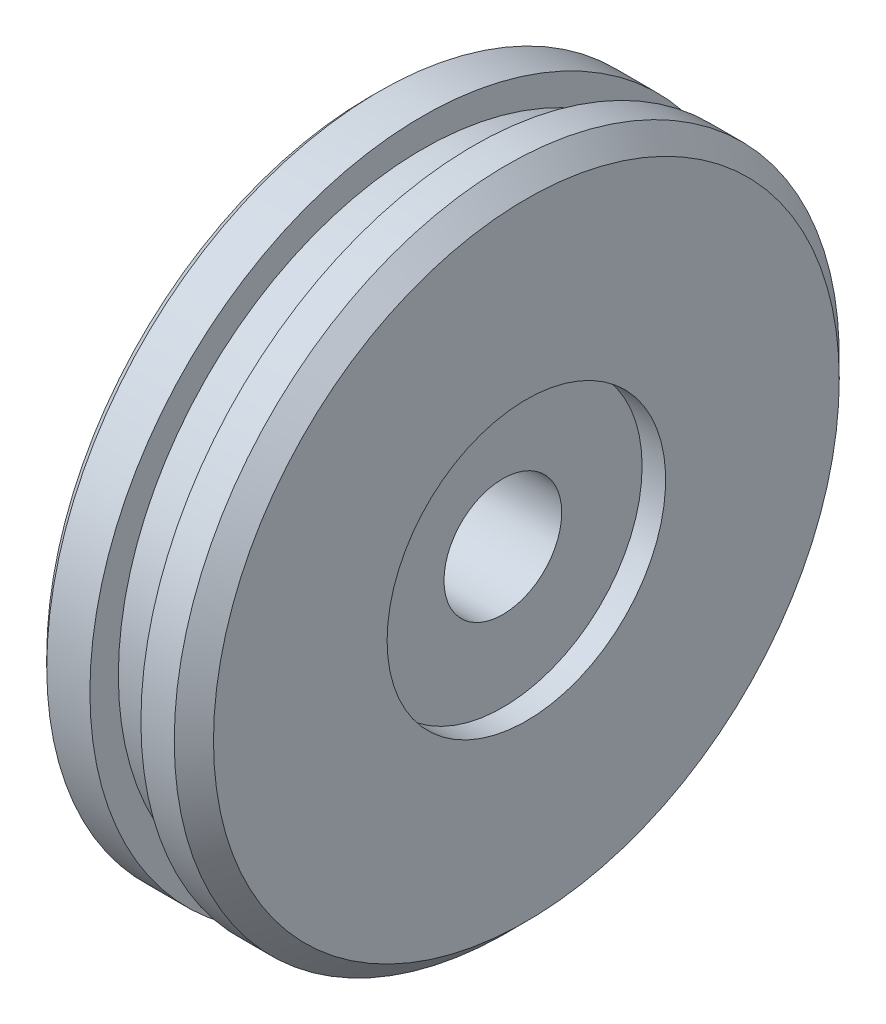
SolidWorks part; units mm, degrees
ref_plane "Front Plane" through (0, 0, 0) normal (0, 0, 1) x (1, 0, 0)
ref_plane "Top Plane" through (0, 0, 0) normal (0, 1, 0) x (1, 0, 0)
ref_plane "Right Plane" through (0, 0, 0) normal (1, 0, 0) x (0, 0, -1)
ref_plane "Plane1" through (0, 0, 66) normal (0, 0, 1) x (1, 0, 0)
sketch "Sketch1" plane through (0, 0, 66) normal (0, 0, 1) x (1, 0, 0)
  line L0 (72.2, -65) -> (90.2, -65) construction
  line L1 (77.2, -65) -> (85.2, -65)
  line L2 (85.2, -65) -> (85.2, -49.05)
  line L3 (85.2, -49.05) -> (84.2, -48.05)
  line L4 (84.2, -48.05) -> (77.7, -48.05)
  line L5 (77.7, -48.05) -> (77.2, -48.55)
  line L6 (77.2, -48.55) -> (77.2, -65)
revolve "Revolve1" add sketch "Sketch1" angle 360 about L0
sketch "Sketch2" plane through (0, 0, 66) normal (0, 0, 1) x (1, 0, 0)
  line L0 (74.9, -65) -> (87.5, -65) construction
  line L1 (79.9, -49.5) -> (82.5, -49.5)
  line L2 (82.5, -49.5) -> (82.5, -47.05)
  line L3 (82.5, -47.05) -> (79.9, -47.05)
  line L4 (79.9, -47.05) -> (79.9, -49.5)
revolve "Revolve2" add sketch "Sketch2" angle 360 about L0
combine bodies "Combine1" operation type subtract main body 101 bodies to subtract 102
sketch "Sketch3" plane through (0, 0, 0) normal (0, 0, 1) x (1, 0, 0)
  line L1 (76.7, -76.5) -> (79, -76.5)
  line L2 (76.7, -76.5) -> (76.7, -53.5)
  line L3 (76.7, -53.5) -> (79, -53.5)
  line L4 (79, -76.5) -> (79, -53.5)
extrude "Boss-Extrude1" add sketch "Sketch3" along normal blind 6.6 from offset 62.7 separate body
combine bodies "Combine2" operation type subtract main body 103 bodies to subtract 104
sketch "Sketch4" plane through (0, 0, 0) normal (0, 0, 1) x (1, 0, 0)
  line L1 (76.7, -68.3) -> (79, -68.3)
  line L2 (76.7, -68.3) -> (76.7, -61.7)
  line L3 (76.7, -61.7) -> (79, -61.7)
  line L4 (79, -68.3) -> (79, -61.7)
extrude "Boss-Extrude2" add sketch "Sketch4" along normal blind 23 from offset 54.5 separate body
combine bodies "Combine3" operation type subtract main body 105 bodies to subtract 106
sketch "Sketch5" plane through (0, 0, 0) normal (1, 0, 0) x (0, 0, -1)
  circle A0 centre (-66, -65) radius 4.6
extrude "Boss-Extrude3" add sketch "Sketch5" along normal blind 2.3 from offset 76.7 separate body
combine bodies "Combine4" operation type subtract main body 107 bodies to subtract 108
sketch "Sketch6" plane through (0, 0, 0) normal (1, 0, 0) x (0, 0, -1)
  circle A0 centre (-66, -65) radius 7.1
extrude "Boss-Extrude4" add sketch "Sketch6" along normal blind 1.7 from offset 84 separate body
combine bodies "Combine5" operation type subtract main body 109 bodies to subtract 110
sketch "Sketch7" plane through (0, 0, 0) normal (1, 0, 0) x (0, 0, -1)
  circle A0 centre (-66, -65) radius 3
extrude "Boss-Extrude5" add sketch "Sketch7" along normal blind 5.2 from offset 78.9 separate body
combine bodies "Combine6" operation type subtract main body 111 bodies to subtract 112
sketch "Sketch8" plane through (0, 0, 0) normal (0, 0, 1) x (1, 0, 0)
  line L1 (78.9, -59.5) -> (83, -59.5)
  line L2 (78.9, -59.5) -> (78.9, -57.4)
  line L3 (78.9, -57.4) -> (83, -57.4)
  line L4 (83, -59.5) -> (83, -57.4)
extrude "Boss-Extrude6" add sketch "Sketch8" along normal blind 1.8 from offset 65.1 separate body
combine bodies "Combine7" operation type subtract main body 113 bodies to subtract 114
sketch "Sketch9" plane through (0, 0, 0) normal (0, 0, 1) x (1, 0, 0)
  line L1 (78.9, -65.9) -> (83, -65.9)
  line L2 (78.9, -65.9) -> (78.9, -64.1)
  line L3 (78.9, -64.1) -> (83, -64.1)
  line L4 (83, -65.9) -> (83, -64.1)
extrude "Boss-Extrude7" add sketch "Sketch9" along normal blind 2.1 from offset 71.5 separate body
combine bodies "Combine8" operation type subtract main body 115 bodies to subtract 116
sketch "Sketch10" plane through (0, 0, 0) normal (0, 0, 1) x (1, 0, 0)
  line L1 (78.9, -72.6) -> (83, -72.6)
  line L2 (78.9, -72.6) -> (78.9, -70.5)
  line L3 (78.9, -70.5) -> (83, -70.5)
  line L4 (83, -72.6) -> (83, -70.5)
extrude "Boss-Extrude8" add sketch "Sketch10" along normal blind 1.8 from offset 65.1 separate body
combine bodies "Combine9" operation type subtract main body 117 bodies to subtract 118
sketch "Sketch11" plane through (0, 0, 0) normal (0, 0, 1) x (1, 0, 0)
  line L1 (78.9, -65.9) -> (83, -65.9)
  line L2 (78.9, -65.9) -> (78.9, -64.1)
  line L3 (78.9, -64.1) -> (83, -64.1)
  line L4 (83, -65.9) -> (83, -64.1)
extrude "Boss-Extrude9" add sketch "Sketch11" along normal blind 2.1 from offset 58.4 separate body
combine bodies "Combine10" operation type subtract main body 119 bodies to subtract 120
sketch "Sketch12" plane through (0, 0, 0) normal (0, 0, 1) x (1, 0, 0)
  line L1 (78.9, -57.4) -> (84.2, -57.4)
  line L2 (78.9, -57.4) -> (78.9, -55)
  line L3 (78.9, -55) -> (84.2, -55)
  line L4 (84.2, -57.4) -> (84.2, -55)
extrude "Boss-Extrude10" add sketch "Sketch12" along normal blind 1.8 from offset 65.1 separate body
combine bodies "Combine11" operation type subtract main body 121 bodies to subtract 122
sketch "Sketch13" plane through (0, 0, 0) normal (0, 0, 1) x (1, 0, 0)
  line L1 (78.9, -65.9) -> (84.2, -65.9)
  line L2 (78.9, -65.9) -> (78.9, -64.1)
  line L3 (78.9, -64.1) -> (84.2, -64.1)
  line L4 (84.2, -65.9) -> (84.2, -64.1)
extrude "Boss-Extrude11" add sketch "Sketch13" along normal blind 2.4 from offset 73.6 separate body
combine bodies "Combine12" operation type subtract main body 123 bodies to subtract 124
sketch "Sketch14" plane through (0, 0, 0) normal (0, 0, 1) x (1, 0, 0)
  line L1 (78.9, -75) -> (84.2, -75)
  line L2 (78.9, -75) -> (78.9, -72.6)
  line L3 (78.9, -72.6) -> (84.2, -72.6)
  line L4 (84.2, -75) -> (84.2, -72.6)
extrude "Boss-Extrude12" add sketch "Sketch14" along normal blind 1.8 from offset 65.1 separate body
combine bodies "Combine13" operation type subtract main body 125 bodies to subtract 126
sketch "Sketch15" plane through (0, 0, 0) normal (0, 0, 1) x (1, 0, 0)
  line L1 (78.9, -65.9) -> (84.2, -65.9)
  line L2 (78.9, -65.9) -> (78.9, -64.1)
  line L3 (78.9, -64.1) -> (84.2, -64.1)
  line L4 (84.2, -65.9) -> (84.2, -64.1)
extrude "Boss-Extrude13" add sketch "Sketch15" along normal blind 2.4 from offset 56 separate body
combine bodies "Combine14" operation type subtract main body 127 bodies to subtract 128
